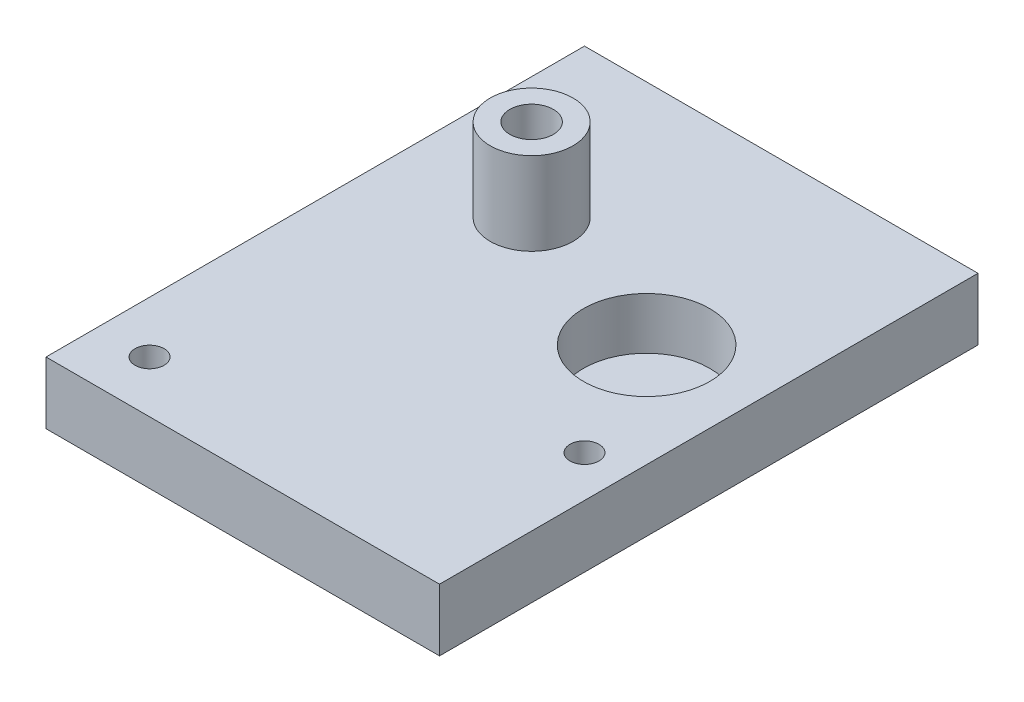
SolidWorks part; units mm, degrees
ref_plane "前视基准面" through (0, 0, 0) normal (0, 0, 1) x (1, 0, 0)
ref_plane "上视基准面" through (0, 0, 0) normal (0, 1, 0) x (1, 0, 0)
ref_plane "右视基准面" through (0, 0, 0) normal (1, 0, 0) x (0, 0, -1)
other "Configuration Table"
sketch "草图1" plane through (0, 0, 0) normal (0, 1, 0) x (1, 0, 0)
  line L1 (-14, 11) -> (5, 11)
  line L2 (-14, 11) -> (-14, -15)
  line L3 (-14, -15) -> (5, -15)
  line L4 (5, 11) -> (5, -15)
  circle A0 centre (0, 0) radius 3.05
  circle A2 centre (-8.1071, 2.5542) radius 1.05
  circle A3 centre (-6.6941, -4.3806) radius 1.05
  circle A4 centre (-8.1071, 2.5542) radius 2
  dimension "D5" = 6.1
  dimension "D6" = 2.1
  dimension "D8" = 2.1
  dimension "D7" = 4
  dimension "D1" = 11
  dimension "D2" = 14
  dimension "D3" = 5
  dimension "D4" = 15
extrude "凸台-拉伸1" add sketch "草图1" along normal blind 3 contours L2 L3 L4 L1
extrude "切除-拉伸1" cut sketch "草图1<3>" against normal blind 2.5 from surface contours A2 | A0 starting at face at (-4.5, 3, 2)
sketch "草图1<3>" plane through (0, 0, 0) normal (0, 1, 0) x (1, 0, 0) same geometry as "草图1"
sketch "草图2" plane through (0, 0, 0) normal (0, -1, 0) x (1, 0, 0)
  circle A0 centre (-11.5, 12.5) radius 1
  circle A1 centre (-11.5, 12.5) radius 0.7
  circle A2 centre (3, 6) radius 1
  circle A3 centre (3, 6) radius 0.7
  dimension "D1" = 2
  dimension "D2" = 1.4
extrude "切除-拉伸2" cut sketch "草图2" against normal blind 1.5 contours A0 | A2
extrude "切除-拉伸3" cut sketch "草图2<3>" against normal through all contours A1 | A3
sketch "草图2<3>" plane through (0, 0, 0) normal (0, -1, 0) x (1, 0, 0) same geometry as "草图2"
extrude "凸台-拉伸2" add sketch "草图1<6>" along normal blind 4 from surface contours A4 starting at face at (-11.5, 3, 11.8)
sketch "草图1<6>" plane through (0, 0, 0) normal (0, 1, 0) x (1, 0, 0) same geometry as "草图1"
sketch "草图3" plane through (0, 0, -11) normal (0, 0, 1) x (1, 0, 0)
  circle A0 centre (0.8, 1.5) radius 0.3
  circle A1 centre (-4.2, 1.5) radius 0.3
  dimension "D1" = 0.6
extrude "切除-拉伸5" cut sketch "草图1<7>" against normal blind 4 from surface contours A2 starting at face at (-8.1071, 7, -4.5542)
sketch "草图1<7>" plane through (0, 0, 0) normal (0, 1, 0) x (1, 0, 0) same geometry as "草图1"
extrude "切除-拉伸6" cut sketch "草图3" along normal blind 1.5 contours A1 | A0
